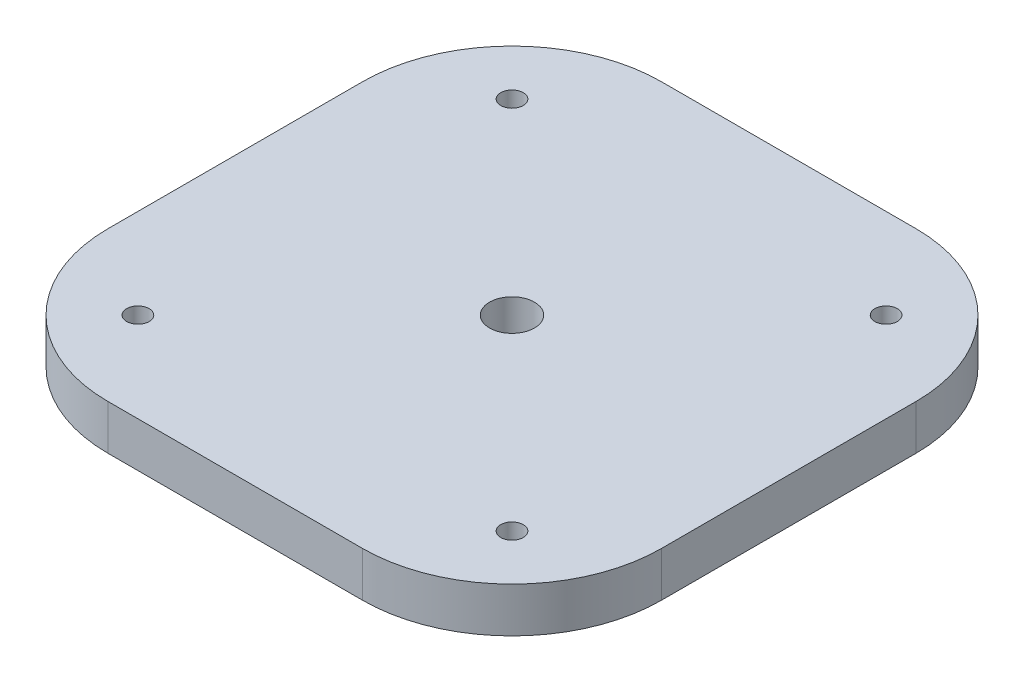
SolidWorks part; units mm, degrees
material "ABS"
ref_plane "Спереди" through (0, 0, 0) normal (0, 0, 1) x (1, 0, 0)
ref_plane "Сверху" through (0, 0, 0) normal (0, 1, 0) x (1, 0, 0)
ref_plane "Справа" through (0, 0, 0) normal (1, 0, 0) x (0, 0, -1)
sketch "Эскиз1" plane through (0, 0, 0) normal (0, 1, 0) x (1, 0, 0)
  line L1 (17, -37) -> (-17, -37)
  line L2 (37, -17) -> (37, 17)
  line L3 (17, 37) -> (-17, 37)
  line L4 (-37, -17) -> (-37, 17)
  line L5 (37, -37) -> (-37, 37) construction
  line L6 (37, 37) -> (-37, -37) construction
  arc A0 (37, 17) -> (17, 37) centre (17, 17) ccw
  arc A1 (17, -37) -> (37, -17) centre (17, -17) ccw
  arc A2 (-17, -37) -> (-37, -17) centre (-17, -17) cw
  arc A3 (-17, 37) -> (-37, 17) centre (-17, 17) ccw
  point P0 (0, 0)
  dimension "D3" = 20
  dimension "D1" = 74
  dimension "D2" = 74
extrude "Бобышка-Вытянуть1" add sketch "Эскиз1" along normal blind 6
sketch "Эскиз2" plane through (0, 0, 0) normal (0, 1, 0) x (1, 0, 0)
  line L1 (25, -25) -> (-25, -25)
  line L2 (25, -25) -> (25, 25)
  line L3 (25, 25) -> (-25, 25)
  line L4 (-25, -25) -> (-25, 25)
  line L5 (25, -25) -> (-25, 25) construction
  line L6 (25, 25) -> (-25, -25) construction
  circle A0 centre (-25, 25) radius 1.5
  circle A1 centre (25, 25) radius 1.5
  circle A2 centre (25, -25) radius 1.5
  circle A3 centre (-25, -25) radius 1.5
  circle A4 centre (0, 0) radius 3
  point P0 (0, 0)
  dimension "D1" = 3
  dimension "D4" = 6
  dimension "D2" = 50
  dimension "D3" = 50
extrude "Вырез-Вытянуть1" cut sketch "Эскиз2" along normal blind 6 contours A0 | A1 | A2 | A3 | A4
sketch "Эскиз3" plane through (0, 0, 0) normal (0, 1, 0) x (1, 0, 0)
  line L1 (-26.7321, 28) -> (-28.4641, 25)
  line L2 (-28.4641, 25) -> (-26.7321, 22)
  line L3 (-26.7321, 22) -> (-23.2679, 22)
  line L4 (-23.2679, 22) -> (-21.5359, 25)
  line L5 (-21.5359, 25) -> (-23.2679, 28)
  line L6 (-23.2679, 28) -> (-26.7321, 28)
  line L7 (23.2679, 28) -> (21.5359, 25)
  line L8 (21.5359, 25) -> (23.2679, 22)
  line L9 (23.2679, 22) -> (26.7321, 22)
  line L10 (26.7321, 22) -> (28.4641, 25)
  line L11 (28.4641, 25) -> (26.7321, 28)
  line L12 (26.7321, 28) -> (23.2679, 28)
  line L13 (23.2679, -22) -> (21.5359, -25)
  line L14 (21.5359, -25) -> (23.2679, -28)
  line L15 (23.2679, -28) -> (26.7321, -28)
  line L16 (26.7321, -28) -> (28.4641, -25)
  line L17 (28.4641, -25) -> (26.7321, -22)
  line L18 (26.7321, -22) -> (23.2679, -22)
  line L19 (-26.7321, -22) -> (-28.4641, -25)
  line L20 (-28.4641, -25) -> (-26.7321, -28)
  line L21 (-26.7321, -28) -> (-23.2679, -28)
  line L22 (-23.2679, -28) -> (-21.5359, -25)
  line L23 (-21.5359, -25) -> (-23.2679, -22)
  line L24 (-23.2679, -22) -> (-26.7321, -22)
  circle A0 centre (-25, 25) radius 3 construction
  circle A1 centre (25, 25) radius 3 construction
  circle A2 centre (25, -25) radius 3 construction
  circle A3 centre (-25, -25) radius 3 construction
  dimension "6" = 6
extrude "Вырез-Вытянуть2" cut sketch "Эскиз3" along normal blind 2
sketch "Эскиз4" plane through (0, 0, 0) normal (0, 1, 0) x (1, 0, 0)
  arc A0 (-37, -17) -> (-17, -37) centre (-17, -17) ccw construction
  arc A1 (17, -37) -> (37, -17) centre (17, -17) ccw construction
  arc A2 (37, 17) -> (17, 37) centre (17, 17) ccw construction
  arc A3 (-17, 37) -> (-37, 17) centre (-17, 17) ccw construction
  arc A4 (-37, -17) -> (-17, -37) centre (-17, -17) ccw
  arc A5 (17, -37) -> (37, -17) centre (17, -17) ccw
  arc A6 (37, 17) -> (17, 37) centre (17, 17) ccw
  arc A7 (-17, 37) -> (-37, 17) centre (-17, 17) ccw
  circle A8 centre (0, 67.5941) radius 35
  circle A9 centre (67.5941, 0.9713) radius 35
  circle A10 centre (0.9713, -66.6228) radius 35
  circle A11 centre (-66.6228, 0) radius 35
  point P23 (0.4857, 0.4857)
  dimension "D1" = 70
  dimension "D2" = 4
extrude "Вырез-Вытянуть3" [suppressed] cut sketch "Эскиз4" along normal through all contours A11 | A8 | A9 | A10
equation "\"D2@Эскиз1\"=\"D1@Эскиз1\""
equation "\"D3@Эскиз2\"=\"D2@Эскиз2\""
